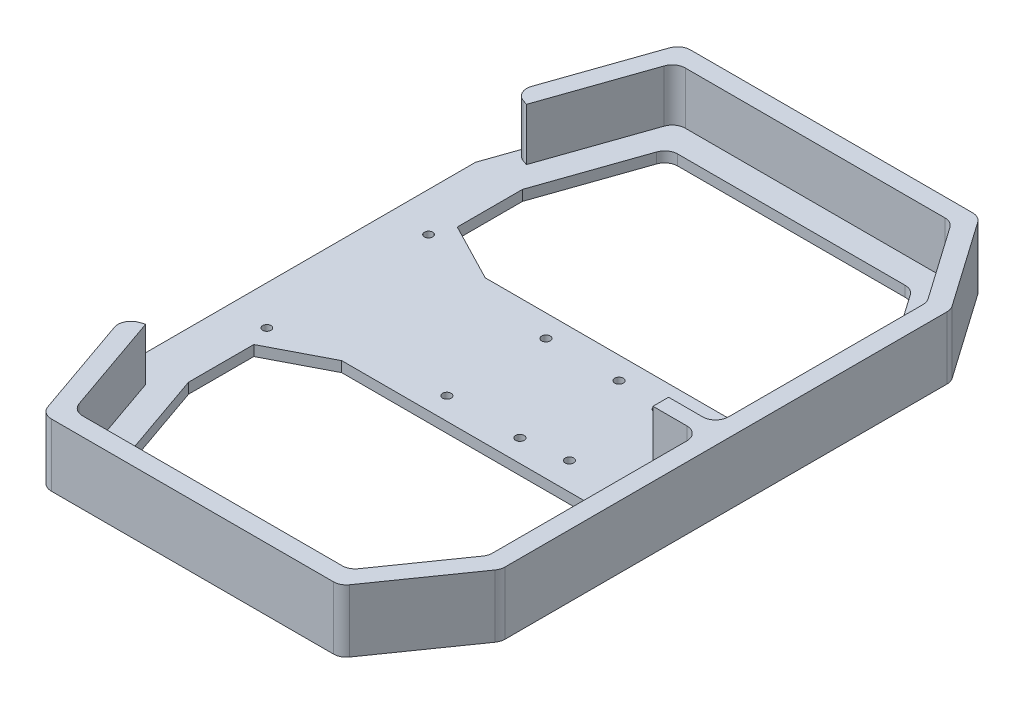
SolidWorks part; units mm, degrees
ref_plane "Front Plane" through (0, 0, 0) normal (0, 0, 1) x (1, 0, 0)
ref_plane "Top Plane" through (0, 0, 0) normal (0, 1, 0) x (1, 0, 0)
ref_plane "Right Plane" through (0, 0, 0) normal (1, 0, 0) x (0, 0, -1)
sketch "Sketch1" plane through (0, 0, 0) normal (0, 1, 0) x (1, 0, 0)
  line L0 (0, 0) -> (59180.0483, 0) construction
  line L1 (0, 0) -> (0, 59180.0483) construction
  line L2 (-15, -39) -> (-15, 39)
  line L5 (25.198, 27.5) -> (128, 27.5)
  line L6 (128, 27.5) -> (128, 80.9254)
  line L7 (110.7927, 105.5) -> (17.4422, 105.5)
  line L17 (25.198, -27.5) -> (128, -27.5)
  line L20 (5.3583, 122.5) -> (-15, 64)
  line L21 (-15, 64) -> (-15, 39)
  line L22 (3, 39) -> (3, 64)
  line L23 (3, 64) -> (17.4422, 105.5)
  line L24 (3, 39) -> (25.198, 27.5)
  line L26 (3, -39) -> (25.198, -27.5)
  line L27 (3, -39) -> (3, -64)
  line L28 (3, -64) -> (17.4422, -105.5)
  line L31 (5.3583, -122.5) -> (-15, -64)
  line L32 (-15, -39) -> (-15, -64)
  line L33 (-15, 64) -> (3, 64) construction
  line L34 (110.7927, 105.5) -> (128, 80.9254)
  line L35 (5.3583, 122.5) -> (119.6423, 122.5)
  line L36 (119.6423, 122.5) -> (145, 86.2855)
  line L37 (145, 86.2855) -> (145, -86.2855)
  line L38 (128, -27.5) -> (128, -80.9254)
  line L39 (119.6423, -122.5) -> (145, -86.2855)
  line L40 (110.7927, -105.5) -> (128, -80.9254)
  line L41 (110.7927, -105.5) -> (17.4422, -105.5)
  line L42 (5.3583, -122.5) -> (119.6423, -122.5)
  circle A0 centre (0, 31) radius 1.6
  circle A1 centre (0, -31) radius 1.6
  point P20 (145, 0)
  point P21 (140, 0)
  point P29 (-15, 0)
  point P36 (123.9671, 105.5)
  point P37 (127.0959, 88.4378)
  point P38 (128, 82.7644)
  dimension "D1" = 3.2
  dimension "D2" = 62
  dimension "D3" = 78
  dimension "D4" = 15
  dimension "D9" = 55
  dimension "D5" = 25
  dimension "D8" = 25
  dimension "D11" = 78
  dimension "D12" = 125
  dimension "D13" = 18
  dimension "D14" = 25
  dimension "D6" = 17
  dimension "D7" = 17
  dimension "D10" = 17
  dimension "D15" = 17
  dimension "D16" = 30
  dimension "D17" = 125
extrude "Boss-Extrude1" add sketch "Sketch1" along normal mid plane 4
sketch "Sketch2" plane through (0, 2, 0) normal (0, 1, 0) x (1, 0, 0)
  line L0 (0, 0) -> (50000, 0) construction
  circle A0 centre (57, 19) radius 1.65
  circle A1 centre (85, 19) radius 1.65
  circle A2 centre (102, 17) radius 1.65
  circle A3 centre (102, -17) radius 1.65
  circle A4 centre (85, -19) radius 1.65
  circle A5 centre (57, -19) radius 1.65
  dimension "D1" = 3.3
  dimension "D2" = 3.3
  dimension "D3" = 3.3
sketch "Sketch3" plane through (0, 2, 0) normal (0, 1, 0) x (1, 0, 0)
  line L0 (120, -3) -> (120, 3)
  line L1 (-200000, 0) -> (250000, 0) construction
  line L2 (120, 3) -> (138, 3)
  line L3 (138, 3) -> (138, 84.0784)
  line L4 (138, 84.0784) -> (115.9984, 115.5)
  line L5 (115.9984, 115.5) -> (10.334, 115.5)
  line L6 (10.334, 115.5) -> (-4.4642, 72.9771)
  line L7 (-4.4642, 72.9771) -> (-11.0753, 75.2778)
  line L8 (5.3583, 122.5) -> (-15, 64) construction
  line L9 (-11.0753, 75.2778) -> (5.3583, 122.5)
  line L10 (5.3583, 122.5) -> (119.6423, 122.5)
  line L11 (119.6423, 122.5) -> (145, 86.2855)
  line L12 (145, 86.2855) -> (145, -86.2855)
  line L13 (145, -86.2855) -> (145, 86.2855) construction
  line L14 (0, 0) -> (50000, 0) construction
  line L15 (119.6423, -122.5) -> (145, -86.2855)
  line L16 (5.3583, -122.5) -> (119.6423, -122.5)
  line L17 (-11.0753, -75.2778) -> (5.3583, -122.5)
  line L18 (-4.4642, -72.9771) -> (-11.0753, -75.2778)
  line L19 (10.334, -115.5) -> (-4.4642, -72.9771)
  line L20 (115.9984, -115.5) -> (10.334, -115.5)
  line L21 (138, -84.0784) -> (115.9984, -115.5)
  line L22 (138, -3) -> (138, -84.0784)
  line L23 (120, -3) -> (138, -3)
  point P25 (145, 0)
  point P34 (120, 0)
  dimension "D1" = 6
  dimension "D2" = 25
  dimension "D3" = 7
  dimension "D4" = 7
  dimension "D5" = 7
  dimension "D6" = 7
  dimension "D7" = 50
extrude "Boss-Extrude2" add sketch "Sketch3" along normal blind 20
fillet "Fillet1" radius 5 19 edges at (-11.0753, 12, 75.2778) (119.6423, 10, -122.5) (145, 10, -86.2855) (145, 10, 86.2855) (119.6423, 10, 122.5) (5.3583, 10, 122.5) (5.3583, 10, -122.5) (-11.0753, 12, -75.2778) (10.334, 12, 115.5) (115.9984, 12, 115.5) (138, 12, 84.0784) (138, 12, 3) (138, 12, -3) (17.4422, 0, -105.5) (128, 0, -80.9254) (110.7927, 0, -105.5) (138, 12, -84.0784) (115.9984, 12, -115.5) (10.334, 12, -115.5)
extrude "Cut-Extrude1" cut sketch "Sketch2" against normal through all
equation "\"D8@Sketch1\"=\"D5@Sketch1\""
equation "\"D2@Sketch2\"=\"D1@Sketch2\""
equation "\"D3@Sketch2\"=\"D1@Sketch2\""
